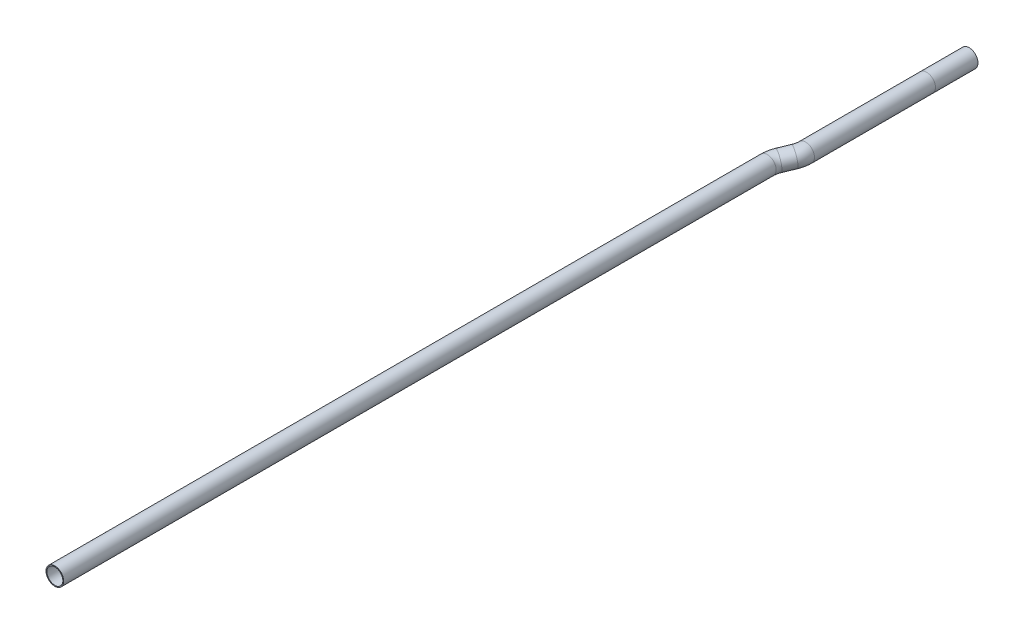
SolidWorks part; units mm, degrees
material "6061 Alloy"
ref_plane "Front Plane" through (0, 0, 0) normal (0, 0, 1) x (1, 0, 0)
ref_plane "Top Plane" through (0, 0, 0) normal (0, 1, 0) x (1, 0, 0)
ref_plane "Right Plane" through (0, 0, 0) normal (1, 0, 0) x (0, 0, -1)
sketch "Sketch1" plane through (0, 0, 0) normal (0, 0, 1) x (1, 0, 0)
  line L0 (0, 0) -> (3.7368, 0.7433) construction
  circle A0 centre (3.7368, 0.7433) radius 2.8575
  circle A1 centre (3.7368, 0.7433) radius 3.175
  dimension "D1" = 6.35
  dimension "D2" = 0.3175
ref_axis "Axis1" through (3.7368, 0.7433, -54.8561) along (0, 0, 1)
ref_plane "Plane1" through (0, 0, 0) normal (-0.1951, 0.9808, 0) x (0, 0, 1)
sketch "Sketch2" plane through (0, 0, 0) normal (-0.1951, 0.9808, 0) x (0, 0, 1)
  line L0 (0, 0) -> (0, 3.81) construction
  line L1 (0, 3.81) -> (-12.7, 3.81)
  line L2 (0, 3.81) -> (2.54, 3.81)
  line L3 (7.0301, 5.6699) -> (12.2004, 10.8401) construction
  line L4 (16.6905, 12.7) -> (37.9195, 12.7) construction
  line L5 (42.4096, 10.8401) -> (51.3899, 1.8599) construction
  line L6 (55.88, 0) -> (311.15, 0)
  line L8 (0, 0) -> (36.3164, 0) construction
  line L9 (290.83, 3.175) -> (290.83, -3.175) construction
  line L10 (76.2, 3.175) -> (76.2, -3.175) construction
  line L11 (0, 0.635) -> (0, 6.985) construction
  line L12 (2.54, 3.81) -> (45.8779, 3.81)
  line L13 (49.0529, 2.9593) -> (52.705, 0.8507)
  arc A0 (2.54, 3.81) -> (7.0301, 5.6699) centre (2.54, 10.16) ccw construction
  arc A1 (12.2004, 10.8401) -> (16.6905, 12.7) centre (16.6905, 6.35) cw construction
  arc A2 (37.9195, 12.7) -> (42.4096, 10.8401) centre (37.9195, 6.35) cw construction
  arc A3 (51.3899, 1.8599) -> (55.88, 0) centre (55.88, 6.35) ccw construction
  arc A4 (45.8779, 3.81) -> (49.0529, 2.9593) centre (45.8779, -2.54) cw
  arc A5 (52.705, 0.8507) -> (55.88, 0) centre (55.88, 6.35) ccw
  dimension "D3" = 6.35
  dimension "D4" = 6.35
  dimension "D5" = 6.35
  dimension "D6" = 6.35
  dimension "D13" = 6.35
  dimension "D14" = 6.35
  dimension "D1" = 3.81
  dimension "D2" = 12.7
  dimension "D7" = 20.32
  dimension "D8" = 12.7
  dimension "D9" = 135
  dimension "D10" = 135
  dimension "D11" = 20.32
  dimension "D12" = 2.54
  dimension "D15" = 30
sweep "Sweep1" add profiles "Sketch1" path "Sketch2"
